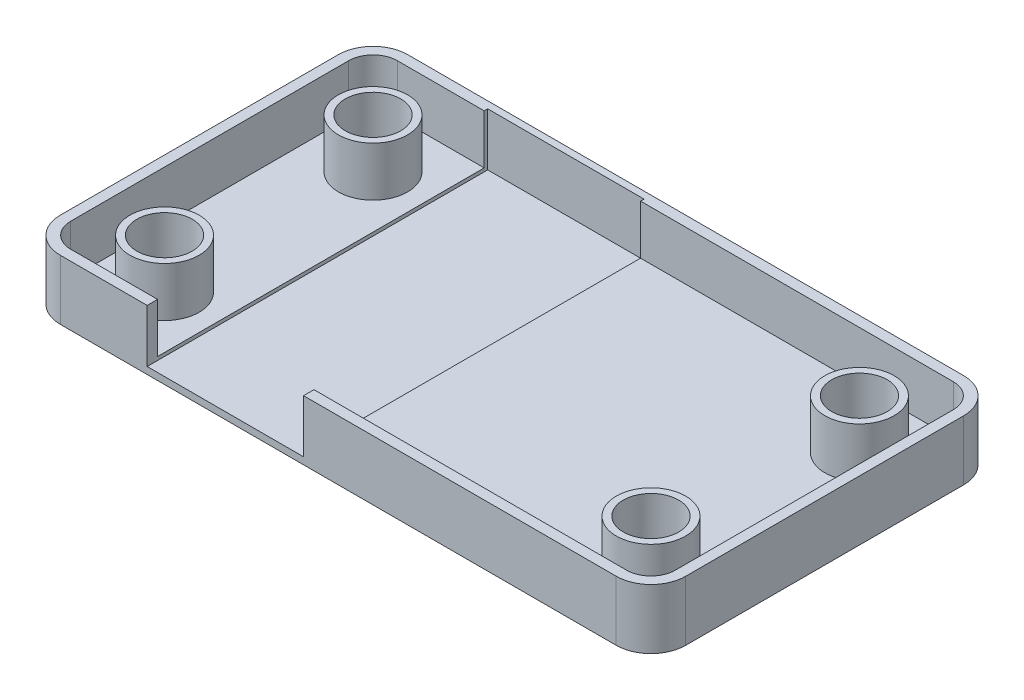
SolidWorks part; units mm, degrees
ref_plane "Front Plane" through (0, 0, 0) normal (0, 0, 1) x (1, 0, 0)
ref_plane "Top Plane" through (0, 0, 0) normal (0, 1, 0) x (1, 0, 0)
ref_plane "Right Plane" through (0, 0, 0) normal (1, 0, 0) x (0, 0, -1)
sketch "Sketch1" plane through (0, 0, 0) normal (0, 1, 0) x (1, 0, 0)
  line L1 (-80, -50) -> (80, -50)
  line L2 (-90, -40) -> (-90, 40)
  line L3 (-80, 50) -> (80, 50)
  line L4 (90, -40) -> (90, 40)
  line L5 (-90, -50) -> (90, 50) construction
  line L6 (-90, 50) -> (90, -50) construction
  arc A0 (-80, -50) -> (-90, -40) centre (-80, -40) cw
  arc A1 (-90, 40) -> (-80, 50) centre (-80, 40) cw
  arc A2 (80, -50) -> (90, -40) centre (80, -40) ccw
  arc A3 (80, 50) -> (90, 40) centre (80, 40) cw
  point P0 (0, 0)
  dimension "D3" = 10
  dimension "D1" = 180
  dimension "D2" = 100
extrude "Boss-Extrude1" add sketch "Sketch1" along normal blind 20 contours L3 A3 L4 A2 L1 A0 L2 A1
shell "Shell1" thickness 3 removed face at (0, 20, 0)
sketch "Sketch3" plane through (0, 3, 0) normal (0, 1, 0) x (1, 0, 0)
  line L0 (-80, 50) -> (80, 50) construction
  line L2 (-90, -40) -> (-90, 40) construction
  line L3 (-90, 0) -> (90, 0) construction
  line L4 (90, -40) -> (90, 40) construction
  line L5 (0, 47) -> (0, -50) construction
  line L6 (-80, 47) -> (80, 47) construction
  line L7 (-80, -50) -> (80, -50) construction
  circle A0 centre (-70, 30) radius 9.9729
  circle A1 centre (-70, 30) radius 7.9729
  circle A2 centre (70, 30) radius 7.9729
  circle A3 centre (70, 30) radius 9.9729
  circle A4 centre (70, -30) radius 7.9729
  circle A5 centre (70, -30) radius 9.9729
  circle A6 centre (-70, -30) radius 7.9729
  circle A7 centre (-70, -30) radius 9.9729
  dimension "D1" = 20
  dimension "D2" = 20
  dimension "D3" = 2
extrude "Boss-Extrude2" add sketch "Sketch3" along normal blind 18
sketch "Sketch4" plane through (0, 0, 50) normal (0, 0, 1) x (1, 0, 0)
  line L0 (-80, 20) -> (80, 20) construction
  line L1 (-55, 18) -> (-10, 18)
  line L2 (-55, 18) -> (-55, 2)
  line L3 (-55, 2) -> (-10, 2)
  line L4 (-10, 18) -> (-10, 2)
  line L5 (-80, 0) -> (80, 0) construction
  line L6 (-90, 20) -> (-90, 0) construction
  line L7 (90, 20) -> (90, 0) construction
  dimension "D1" = 2
  dimension "D2" = 2
  dimension "D3" = 35
  dimension "D4" = 100
extrude "Cut-Extrude2" cut sketch "Sketch4" against normal blind 98
sketch "Sketch5" plane through (0, 0, 50) normal (0, 0, 1) x (1, 0, 0)
  line L1 (-92.8699, 26.8124) -> (103.865, 26.8124)
  line L2 (-92.8699, 26.8124) -> (-92.8699, 17.2279)
  line L3 (-92.8699, 17.2279) -> (103.865, 17.2279)
  line L4 (103.865, 26.8124) -> (103.865, 17.2279)
extrude "Cut-Extrude3" cut sketch "Sketch5" against normal blind 116
